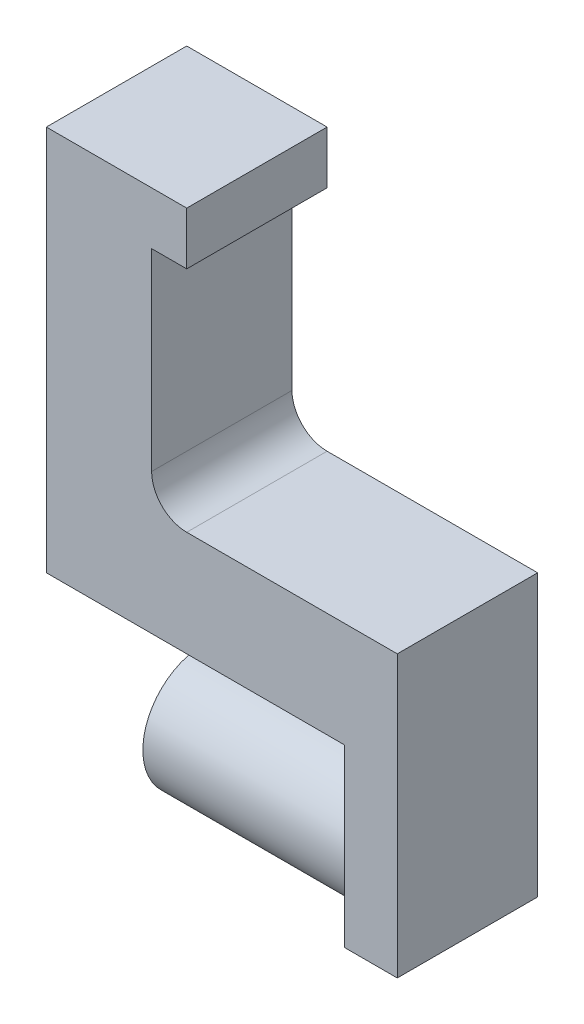
SolidWorks part; units mm, degrees
material "ASTM A36 Steel"
ref_plane "Front Plane" through (0, 0, 0) normal (0, 0, 1) x (1, 0, 0)
ref_plane "Top Plane" through (0, 0, 0) normal (0, 1, 0) x (1, 0, 0)
ref_plane "Right Plane" through (0, 0, 0) normal (1, 0, 0) x (0, 0, -1)
sketch "Sketch1" plane through (0, 0, 0) normal (1, 0, 0) x (0, 0, -1)
  circle A0 centre (0, 0) radius 11.1125
  dimension "D1" = 22.225
extrude "Boss-Extrude1" add sketch "Sketch1" against normal blind 38.1
sketch "Sketch2" plane through (0, 0, 0) normal (0, 0, 1) x (1, 0, 0)
  line L1 (0, -11.1125) -> (9.525, -11.1125)
  line L2 (0, -11.1125) -> (0, 20.6375)
  line L3 (0, 20.6375) -> (9.525, 20.6375)
  line L4 (9.525, -11.1125) -> (9.525, 20.6375)
  dimension "D1" = 9.525
  dimension "D2" = 31.75
  dimension "D3" = 11.1125
extrude "Boss-Extrude2" add sketch "Sketch2" along normal blind 12.7 and the other way blind 12.7
sketch "Sketch3" plane through (0, 0, 0) normal (0, 0, 1) x (1, 0, 0)
  line L1 (-53.975, 20.6375) -> (9.525, 20.6375)
  line L2 (-53.975, 20.6375) -> (-53.975, 39.6875)
  line L3 (-53.975, 39.6875) -> (9.525, 39.6875)
  line L4 (9.525, 20.6375) -> (9.525, 39.6875)
  dimension "D1" = 63.5
  dimension "D2" = 19.05
  dimension "D3" = 20.6375
  dimension "D4" = 53.975
extrude "Boss-Extrude3" add sketch "Sketch3" along normal blind 12.7 and the other way blind 12.7
sketch "Sketch4" plane through (0, 0, 0) normal (0, 0, 1) x (1, 0, 0)
  line L1 (-53.975, 20.6375) -> (-34.925, 20.6375)
  line L2 (-53.975, 20.6375) -> (-53.975, 90.4875)
  line L3 (-53.975, 90.4875) -> (-34.925, 90.4875)
  line L4 (-34.925, 20.6375) -> (-34.925, 90.4875)
  dimension "D3" = 20.6375
  dimension "D4" = 53.975
  dimension "D1" = 19.05
  dimension "D2" = 69.85
extrude "Boss-Extrude4" add sketch "Sketch4" along normal blind 12.7 and the other way blind 12.7
sketch "Sketch5" plane through (0, 0, 0) normal (0, 0, 1) x (1, 0, 0)
  line L5 (-53.975, 77.7875) -> (-41.2394, 77.7875)
  line L6 (-53.975, 90.4875) -> (-53.975, 20.6375) construction
  line L7 (-41.2394, 77.7875) -> (-41.2394, 80.9625)
  line L8 (-41.2394, 80.9625) -> (-28.575, 80.9625)
  line L9 (-28.575, 80.9625) -> (-28.575, 90.4875)
  line L10 (-28.575, 90.4875) -> (-53.975, 90.4875)
  line L11 (-53.975, 90.4875) -> (-53.975, 77.7875)
  dimension "D1" = 12.7
  dimension "D2" = 3.175
  dimension "D3" = 12.6644
  dimension "D4" = 25.4
  dimension "D5" = 90.4875
  dimension "D6" = 53.975
extrude "Boss-Extrude5" add sketch "Sketch5" along normal blind 12.7 and the other way blind 12.7
fillet "Fillet1" radius 6.35 1 edges at (-34.925, 39.6875, 0)
equation "\"F\"= 700"
equation "\"SF\"= 4"
equation "\"Sy\"= 36000"
equation "\"E\"= 29000000"
equation "\"dmax\"= 0.005"
equation "\"LA\"= 1.5"
equation "\"LB\"= 1.25"
equation "\"LC\"= 2.5"
equation "\"LD\"= 1.5"
equation "\"LE\"= 1"
equation "\"W\"= 1"
equation "\"tprac\"= 0.375"
equation "\"step\"= 0.125"
equation "\"slotW\"= 0.4986"
equation "\"slotD\"= 0.125"
equation "\"P\"= \"F\" / 2"
equation "\"sigA\"= \"Sy\" / \"SF\""
equation "\"MA\"= \"P\" * \"LA\""
equation "\"dAmin\"= ( 32 * \"MA\" / ( pi * \"sigA\" ) ) ^ ( 1 / 3 )"
equation "\"dA\"= ( int( \"dAmin\" / \"step\" ) + 1 ) * \"step\""
equation "\"MC\"= \"P\" * \"LC\" / 4"
equation "\"hCmin\"= sqr( 6 * \"MC\" / ( \"W\" * \"sigA\" ) )"
equation "\"hC\"= 0.75"
equation "\"ME\"= ( \"P\" / 2 ) * \"LE\""
equation "\"hEmin\"= sqr( 6 * \"ME\" / ( \"W\" * \"sigA\" ) )"
equation "\"hE\"= ( int( ( \"hEmin\" + \"slotD\" ) / \"step\" ) + 1 ) * \"step\""
equation "\"tB\"= \"tprac\""
equation "\"tD\" = 0.75"
equation "\"yb\"= \"LB\" - \"dA\" / 2"
equation "\"hD\"= \"hC\" + \"LD\" + \"hE\""
equation "\"yD\"= \"yb\" + \"hD\""
equation "\"xl\"= \"LC\" - \"tB\""
equation "\"D1@Sketch1\" = \"dA\""
equation "\"D1@Sketch2\" = \"tB\""
equation "\"D2@Sketch2\" = \"LB\""
equation "\"D3@Sketch2\" = \"dA\" / 2"
equation "\"D1@Sketch3\" = \"LC\""
equation "\"D2@Sketch3\" = \"hC\""
equation "\"D3@Sketch3\" = \"yb\""
equation "\"D4@Sketch3\" = \"xl\""
equation "\"D1@Sketch4\" = \"tD\""
equation "\"D2@Sketch4\" = \"hD\""
equation "\"D1@Sketch5\" = \"hE\""
equation "\"D2@Sketch5\" = \"slotD\""
equation "\"D3@Sketch5\" = \"slotW\""
equation "\"D4@Sketch5\" = \"LE\""
equation "\"D5@Sketch5\"= \"yD\""
